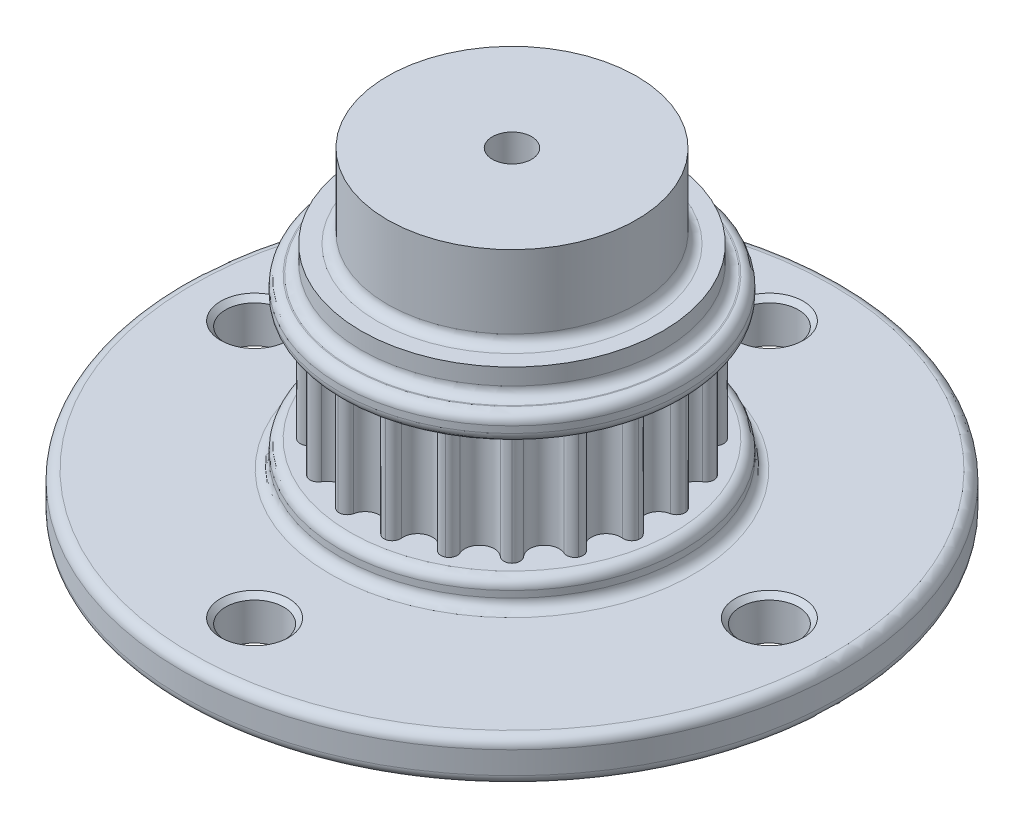
SolidWorks part; units mm, degrees
ref_plane "Front Plane" through (0, 0, 0) normal (0, 0, 1) x (1, 0, 0)
ref_plane "Top Plane" through (0, 0, 0) normal (0, 1, 0) x (1, 0, 0)
ref_plane "Right Plane" through (0, 0, 0) normal (1, 0, 0) x (0, 0, -1)
sketch "Sketch1" plane through (0, 0, 0) normal (0, 1, 0) x (1, 0, 0)
  line L0 (0, 0) -> (0, 9.1676) construction
  line L1 (0, 0) -> (2.731, 8.405) construction
  circle A0 centre (0, 0) radius 9.1676 construction
  circle A1 centre (0, 0) radius 7.9476 construction
  circle A2 centre (0, 8.8376) radius 0.89 construction
  circle A5 centre (2.731, 8.405) radius 0.89 construction
  arc A6 (0, 7.9476) -> (0.8721, 8.6598) centre (0, 8.8376) ccw
  arc A7 (0.8721, 8.6598) -> (1.4405, 9.0537) centre (1.362, 8.5599) cw
  arc A8 (1.4277, 9.0557) -> (1.8466, 8.5054) centre (1.3498, 8.5618) cw
  arc A9 (2.4559, 7.5586) -> (1.8466, 8.5054) centre (2.731, 8.405) cw
  arc A10 (1.4405, 9.0537) -> (1.4277, 9.0557) centre (0, 0) cw
  arc A11 (0, 7.9476) -> (2.4559, 7.5586) centre (0, 0) ccw
  dimension "D1" = 18.3352
  dimension "D3" = 1.78
  dimension "D4" = 0.5
  dimension "D2" = 1.22
  dimension "D5" = 18
extrude "Boss-Extrude1" add sketch "Sketch1" along normal mid plane 7.112 contours A6 A11 A9 A8 A7 region at (0.0089, 0, -0.0564)
ref_axis "Axis1" through (0, 3.3, 0) along (0, -1, 0)
pattern_circular "CirPattern1" count 20 over 360 about axis through (0, 3.3, 0) along (0, -1, 0) of "Boss-Extrude1"
sketch "Sketch2" plane through (0, 0, 0) normal (1, 0, 0) x (0, 0, -1)
  line L10 (0, 3.5) -> (10.3423, 3.5) construction
  line L11 (0, 3.5) -> (0, 5.0875) construction
  line L12 (0, 5.0875) -> (10.3423, 5.0875)
  line L15 (10.3423, 3.5) -> (10.3423, 5.0875) construction
  line L20 (0, 3.3) -> (0, -3.3) construction
  line L22 (10.3423, 5.0875) -> (0, 5.0875) construction
  line L23 (10.3423, 5.0875) -> (10.3423, 3.5)
  line L24 (10.3423, 3.5) -> (0, 3.5)
  line L25 (0, 5.0875) -> (0, 3.5)
  dimension "D1" = 1.5875
  dimension "D2" = 10.3423
  dimension "D3" = 3.5
revolve "Revolve3" add sketch "Sketch2" angle 360 about axis through (0, 3.3, 0) along (0, -1, 0) region at (0, 4.2937, -5.1712)
mirror "Mirror1" about plane through (0, 0, 0) normal (0, 1, 0) of "Revolve3"
sketch "Sketch9" plane through (0, -5.0875, 0) normal (0, -1, 0) x (1, 0, 0)
  circle A0 centre (0, 0) radius 19.8438
  circle A1 centre (0, 0) radius 1.5
  dimension "D1" = 3
  dimension "D2" = 39.6875
extrude "Boss-Extrude2" add sketch "Sketch9" along normal blind 2.54
sketch "Sketch3" plane through (0, 0, 0) normal (0, 1, 0) x (1, 0, 0)
  circle A0 centre (-15.5, 0) radius 1.7462
  circle A3 centre (0, 15.5) radius 1.7462
  circle A4 centre (15.5, 0) radius 1.7463
  circle A5 centre (0, -15.5) radius 1.7462
  dimension "D3" = 3.4925
  dimension "D1" = 15.5
  dimension "D4" = 4
extrude "Cut-Extrude1" cut sketch "Sketch3" against normal through all both and the other way through all
ref_axis "Axis2" through (-15.5, -7.6275, 0) along (0, 1, 0)
sketch "Sketch6" plane through (0, 0, 0) normal (0, 0, 1) x (1, 0, 0)
  line L0 (-19.1322, -3.5) -> (-11.8678, -3.5) construction
  line L1 (-5.7956, -3.5) -> (-6.4824, -3.5) construction
  line L2 (-11.8678, -3.5) -> (-15.5, -7.1322)
  line L3 (-15.5, -7.1322) -> (-19.1322, -3.5) construction
  line L4 (-18.548, -4.0842) -> (-12.452, -4.0842) construction
  line L5 (-17.2462, -3.998) -> (-13.7538, -3.998) construction
  line L8 (-15.5, -7.1322) -> (-15.5, -3.5)
  line L9 (-15.5, -3.5) -> (-11.8678, -3.5)
  line L10 (-15.5, -7.6275) -> (-15.5, -5.0875) construction
  line L12 (-17.2462, -5.0875) -> (-17.2462, -7.6275) construction
  line L13 (-13.7538, -7.6275) -> (-13.7538, -5.0875) construction
  point P2 (-15.5, -3.998)
  dimension "D1" = 6.096
  dimension "D2" = 0.5842
revolve "Cut-Revolve2" cut sketch "Sketch6" angle 360 about axis through (-15.5, -7.6275, 0) along (0, 1, 0)
pattern_circular "CirPattern2" count 4 over 360 about axis through (0, 3.3, 0) along (0, -1, 0) of "Cut-Revolve2"
sketch "Sketch11" plane through (0, -5.0875, 0) normal (0, -1, 0) x (1, 0, 0)
  circle A0 centre (0, 0) radius 1.5
  dimension "D1" = 3
extrude "Cut-Extrude2" cut sketch "Sketch11" against normal blind 6
sketch "Sketch10" plane through (0, 0, 0) normal (1, 0, 0) x (0, 0, -1)
  line L1 (1.1822, 6.675) -> (7.5, 6.675) construction
  line L2 (1.1822, 6.675) -> (1.1822, 11.675)
  line L3 (1.1822, 11.675) -> (7.5, 11.675)
  line L4 (7.5, 6.675) -> (7.5, 11.675)
  line L5 (0, 0) -> (0, 11.675) construction
  line L6 (10.3423, 5.0875) -> (-10.3423, 5.0875) construction
  line L7 (1.1822, 6.675) -> (9.0875, 6.675) construction
  line L8 (1.1822, 6.675) -> (1.1822, 5.0875)
  line L9 (1.1822, 5.0875) -> (9.0875, 5.0875)
  line L10 (9.0875, 6.675) -> (9.0875, 5.0875)
  line L11 (7.5, 6.675) -> (9.0875, 6.675)
  line L12 (0, 11.675) -> (1.1822, 11.675) construction
  dimension "D1" = 2.3644
  dimension "D2" = 5
  dimension "D3" = 1.5875
  dimension "D4" = 1.5875
  dimension "D5" = 15
revolve "Revolve4" add sketch "Sketch10" angle 360 about L5
fillet "Fillet1" radius 0.5953 8 edges at (0, 5.0875, 10.3423) (0, 3.5, 10.3423) (0, -7.6275, -19.8438) (0, -5.0875, -19.8438) (0, 6.675, -7.5) (0, 5.0875, -9.0875) (0, -3.5, 10.3423) (0, -5.0875, 10.3423)
equation "\"TEETH_NUM\"= 20"
equation "\"TOOTH_PITCH\"= 3mm"
equation "\"PITCH_LINE_OFFSET\"= .015in"
equation "\"DIAMETER_PER_GROOVE\"= \"OUTSIDE_DIAMETER\" / \"TEETH_NUM\" * 1in"
equation "\"PITCH_DIAMETER\"= ( ( \"TEETH_NUM\" * 3 - 1.31 ) / 3.1415 + .415 ) * 1mm"
equation "\"OUTSIDE_DIAMETER\"= \"PITCH_DIAMETER\" - \"PITCH_LINE_OFFSET\" * 2"
equation "\"D1@Sketch1\"=\"OUTSIDE_DIAMETER\""
equation "\"TOOTH_HEIGHT\"= 1.22mm"
equation "\"D2@Sketch1\"=\"TOOTH_HEIGHT\""
equation "\"TOOTH_DIAMETER\"= 1.78mm"
equation "\"INTERNAL_RADIUS\"= .5mm"
equation "\"D3@Sketch1\"=\"TOOTH_DIAMETER\""
equation "\"D5@Sketch1\"=360 / \"TEETH_NUM\""
equation "\"D4@Sketch1\"=\"INTERNAL_RADIUS\""
equation "\"D1@CirPattern1\"=\"TEETH_NUM\""
equation "\"BELT_GAP\"= 7mm"
equation "\"D2@Sketch2\"=\"PITCH_DIAMETER\"/2+1/32"
equation "\"D3@Sketch2\"=\"BELT_GAP\"/2"
